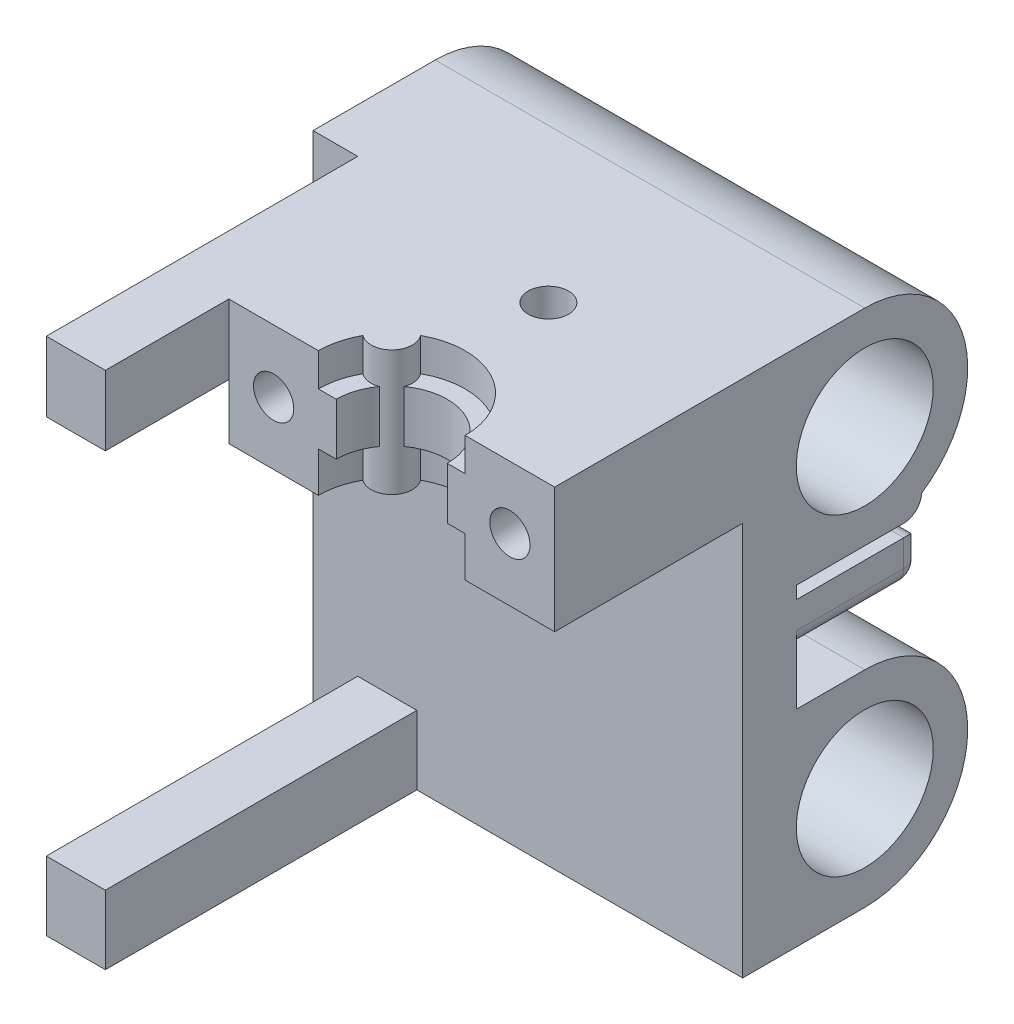
SolidWorks part; units mm, degrees
ref_plane "Front Plane" through (0, 0, 0) normal (0, 0, 1) x (1, 0, 0)
ref_plane "Top Plane" through (0, 0, 0) normal (0, 1, 0) x (1, 0, 0)
ref_plane "Right Plane" through (0, 0, 0) normal (1, 0, 0) x (0, 0, -1)
sketch "Sketch1" plane through (0, 0, 0) normal (0, 0, 1) x (1, 0, 0)
  line L0 (18.2, 14) -> (18.2, 0) construction
  line L1 (0, 0) -> (36.4, 0)
  line L2 (0, 0) -> (0, 14)
  line L3 (0, 14) -> (36.4, 14)
  line L4 (36.4, 0) -> (36.4, 14)
  line L5 (10, 14) -> (10, 0) construction
  line L6 (26.4, 14) -> (26.4, 0) construction
  circle A0 centre (5, 7) radius 2.25 construction
  circle A2 centre (31.4, 7) radius 2.25 construction
  point P9 (0, 7)
  dimension "D1" = 4.5
  dimension "D2" = 16.4
  dimension "D3" = 5
  dimension "D4" = 5
  dimension "D5" = 14
extrude "nozzle clamp 1" add sketch "Sketch1" against normal blind 21
sketch "Sketch2" plane through (0, 14, 0) normal (0, 1, 0) x (1, 0, 0)
  line L0 (36.4, 0) -> (0, 0) construction
  line L1 (10, 0) -> (26.4, 0)
  line L2 (12.4017, 5.7983) -> (18.2, 0) construction
  arc A0 (10, 0) -> (26.4, 0) centre (18.2, 0) cw
  arc A1 (11.0195, 3.9599) -> (14.2401, 7.1805) centre (18.2, 0) cw
  arc A2 (11.0195, 3.9599) -> (14.2401, 7.1805) centre (12.4017, 5.7983) ccw
  point P7 (18.2, 0)
  line M6 (0, 0) -> (36.4, 0)
  dimension "D1" = 2.3
  dimension "D2" = 8.2
  dimension "D3" = 45
extrude "nozzle clamp 2" cut sketch "Sketch2" against normal up to surface (14 mm away) contours A2 L2 L1 A0 | L2 A2 A0 M6 up to face at (18.2, 0, -10.5)
sketch "Sketch3" plane through (0, 0, 0) normal (0, 0, 1) x (1, 0, 0)
  circle A0 centre (5, 7) radius 2.25
  circle A1 centre (5, 7) radius 2.25 construction
  circle A2 centre (31.4, 7) radius 2.25
  circle A3 centre (31.4, 7) radius 2.25 construction
extrude "nozzle clamp heat set inserts" cut sketch "Sketch3" against normal blind 4
sketch "Sketch4" plane through (0, 14, 0) normal (0, 1, 0) x (1, 0, 0)
  line L0 (12, 0) -> (10, 0)
  line L1 (24.4, 0) -> (26.4, 0)
  arc A0 (12, 0) -> (24.4, 0) centre (18.2, 0) cw
  arc A1 (26.4, 0) -> (14.2401, 7.1805) centre (18.2, 0) ccw construction
  arc A2 (10, 0) -> (26.4, 0) centre (18.2, 0) cw
  dimension "D1" = 2
extrude "nozzle clamp 3" add sketch "Sketch4" against normal blind 5.8 from offset 3.7
sketch "Sketch5" plane through (0, 0, -21) normal (0, 0, -1) x (-1, 0, 0)
  line L5 (11.6, 14) -> (11.6, -44)
  line L8 (-36.4, 14) -> (0, 14) construction
  line L9 (-36.4, 14) -> (11.6, 14)
  line L14 (11.6, -44) -> (-36.4, -44)
  line L16 (-36.4, 14) -> (-36.4, -44)
  line L23 (-36.4, 14) -> (11.6, 14) construction
  point P41 (-12.4, 14)
  point P42 (-12.4, 14)
  line M5 (0, 0) -> (0, 14)
  line M6 (0, 14) -> (-36.4, 14)
  line M7 (-36.4, 14) -> (-36.4, 0)
  line M8 (-36.4, 0) -> (0, 0)
  dimension "D1" = 58
  dimension "D2" = 48
  dimension "D9" = 48
extrude "back plate" add sketch "Sketch5" along normal blind 6 contours L16 L14 L5 L9 M8 M5 | M8 M5 M6 M7
sketch "Sketch13" plane through (0, 0, -21) normal (0, 0, 1) x (1, 0, 0)
  line L1 (-6.6, -44) -> (0, -44)
  line L2 (-6.6, -44) -> (-6.6, -36.3)
  line L3 (-6.6, -36.3) -> (0, -36.3)
  line L4 (0, -44) -> (0, -36.3)
  line L5 (-6.6, 14) -> (0, 14)
  line L6 (-6.6, 14) -> (-6.6, 6.2)
  line L7 (-6.6, 6.2) -> (0, 6.2)
  line L8 (0, 14) -> (0, 6.2)
  line L11 (-11.6, -44) -> (36.4, -44) construction
  line L12 (-11.6, 14) -> (-11.6, -44) construction
  line L13 (0, 14) -> (-11.6, 14) construction
  dimension "D1" = 7.7
  dimension "D2" = 7.8
  dimension "D3" = 6.6
  dimension "D4" = 5
extrude "fan shroud mount" add sketch "Sketch13" along normal blind 34.8
sketch "Sketch14" plane through (-6.6, 0, 0) normal (-1, 0, 0) x (0, 0, 1)
  line L0 (13.8, 10.1) -> (-21, 10.1) construction
  line L1 (13.8, 14) -> (13.8, 6.2) construction
  line L4 (13.8, -44) -> (-21, -44) construction
  line L6 (-3.6, 14) -> (-3.6, 6.2) construction
  line L7 (13.8, 14) -> (-21, 14) construction
  line L8 (13.8, 6.2) -> (-21, 6.2) construction
  line L10 (-21, 14) -> (-21, 6.2) construction
  circle A0 centre (-13.6, 10.1) radius 2.25
  circle A2 centre (-13.6, -40) radius 2.25
  circle A4 centre (6.4, -40) radius 2.25
  circle A5 centre (6.4, 10.1) radius 2.25
  point P29 (-21, 10.1)
  dimension "D1" = 4.5
  dimension "D2" = 20
  dimension "D3" = 4
extrude "fan shroud heat set inserts" cut sketch "Sketch14" against normal blind 4
sketch "Sketch16" plane through (0, 14, 0) normal (0, 1, 0) x (1, 0, 0)
  line L0 (18.2, 0) -> (18.2, 17.5) construction
  circle A0 centre (18.2, 17.5) radius 2.25
  dimension "D2" = 4.5
  dimension "D1" = 17.5
extrude "heat set insert for extruder" cut sketch "Sketch16" against normal blind 7
sketch "Sketch17" plane through (-11.6, 0, 0) normal (-1, 0, 0) x (0, 0, 1)
  line L0 (-27, -15) -> (-21, -15) construction
  line L3 (-21, -9) -> (-21, 14)
  line L4 (-21, 14) -> (-34.65, 14)
  line L5 (-21, -9) -> (-34.65, -9)
  line L19 (-27, 14) -> (-27, -44) construction
  line L20 (-21, 14) -> (-21, -44) construction
  line L25 (-21, -21) -> (-34.65, -21)
  line L26 (-21, -44) -> (-34.65, -44)
  line L27 (-21, -21) -> (-21, -44)
  circle A0 centre (-34.65, 2.5) radius 7.65
  circle A2 centre (-34.65, 2.5) radius 11.5 construction
  arc A14 (-34.65, 14) -> (-34.65, -9) centre (-34.65, 2.5) ccw
  circle A15 centre (-34.65, -32.5) radius 11.5 construction
  arc A16 (-34.65, -44) -> (-34.65, -21) centre (-34.65, -32.5) cw
  circle A17 centre (-34.65, -32.5) radius 7.65
  dimension "D2" = 15.3
  dimension "D1" = 35
extrude "linear bearing housing" add sketch "Sketch17" against normal up to surface (48 mm away) up to face at (36.4, -10, -16)
sketch "Sketch18" plane through (-11.6, 0, 0) normal (-1, 0, 0) x (0, 0, 1)
  line L0 (-27, -15) -> (-21, -15) construction
  line L1 (-27, -9) -> (-27, -21) construction
  line L2 (-21, 14) -> (-21, -44) construction
  circle A0 centre (-34.65, 2.5) radius 5.5
  circle A1 centre (-34.65, 2.5) radius 7.65
  circle A2 centre (-34.65, 2.5) radius 7.65 construction
  circle A3 centre (-34.65, -32.5) radius 7.65
  circle A4 centre (-34.65, -32.5) radius 5.5
  dimension "D1" = 11
extrude "Boss-Extrude1" add sketch "Sketch18" against normal blind 3
sketch "Sketch19" plane through (0, 0, -27) normal (0, 0, -1) x (-1, 0, 0)
  line L0 (-36.4, -9) -> (-36.4, -21) construction
  line L1 (-36.4, -10.4) -> (-28.4, -10.4)
  line L2 (-36.4, -10.4) -> (-36.4, -15.4)
  line L3 (-36.4, -15.4) -> (-28.4, -15.4)
  line L4 (-28.4, -10.4) -> (-28.4, -15.4)
  line L5 (-36.4, -9) -> (11.6, -9) construction
  line L6 (11.6, -19.6) -> (3.6, -19.6)
  line L7 (11.6, -19.6) -> (11.6, -14.6)
  line L8 (11.6, -14.6) -> (3.6, -14.6)
  line L9 (3.6, -19.6) -> (3.6, -14.6)
  line L10 (11.6, -9) -> (11.6, -21) construction
  line L11 (11.6, -21) -> (-36.4, -21) construction
  point P13 (11.6, -19.9417)
  dimension "D1" = 1.4
  dimension "D2" = 1.4
  dimension "D3" = 5
  dimension "D4" = 8
  dimension "D5" = 8
extrude "Boss-Extrude2" add sketch "Sketch19" along normal blind 14
sketch "Sketch20" plane through (36.4, 0, 0) normal (1, 0, 0) x (0, 0, -1)
  line L0 (34.65, -9) -> (41, -9)
  line L1 (41, -9) -> (41, -7.0879)
  arc A0 (34.65, -9) -> (34.65, 14) centre (34.65, 2.5) ccw construction
  arc A3 (34.65, -9) -> (34.65, 14) centre (34.65, 2.5) ccw
  arc A4 (34.65, -9) -> (41, -7.0879) centre (34.65, 2.5) ccw
  point P5 (0, 0)
  point P8 (41.32, -6.8681)
  dimension "D1" = 0
extrude "Boss-Extrude3" add sketch "Sketch20" against normal up to surface (8 mm away) up to face at (28.4, -12.9, -34)
sketch "Sketch21" plane through (-11.6, 0, 0) normal (-1, 0, 0) x (0, 0, 1)
  line L0 (-34.65, -21) -> (-41, -21)
  line L1 (-41, -21) -> (-41, -22.9121)
  arc A0 (-34.65, -21) -> (-34.65, -44) centre (-34.65, -32.5) ccw construction
  arc A3 (-34.65, -21) -> (-34.65, -44) centre (-34.65, -32.5) ccw
  arc A4 (-34.65, -21) -> (-41, -22.9121) centre (-34.65, -32.5) ccw
  point P3 (0, 0)
  point P9 (-41.2221, -23.0629)
  dimension "D1" = 0
extrude "Boss-Extrude4" add sketch "Sketch21" against normal up to surface (8 mm away) up to face at (-3.6, -17.1, -34)
fillet "Fillet1" radius 2 14 edges at (-7.6, -19.6, -41) (-3.6, -17.1, -41) (-7.6, -14.6, -41) (-11.6, -17.1, -41) (32.4, -10.4, -41) (28.4, -12.9, -41) (32.4, -15.4, -41) (36.4, -12.9, -41) (32.4, -9, -41) (-7.6, -21, -41) (-11.6, -14.6, -34) (-3.6, -14.6, -34) (28.4, -15.4, -34) (36.4, -15.4, -34)
